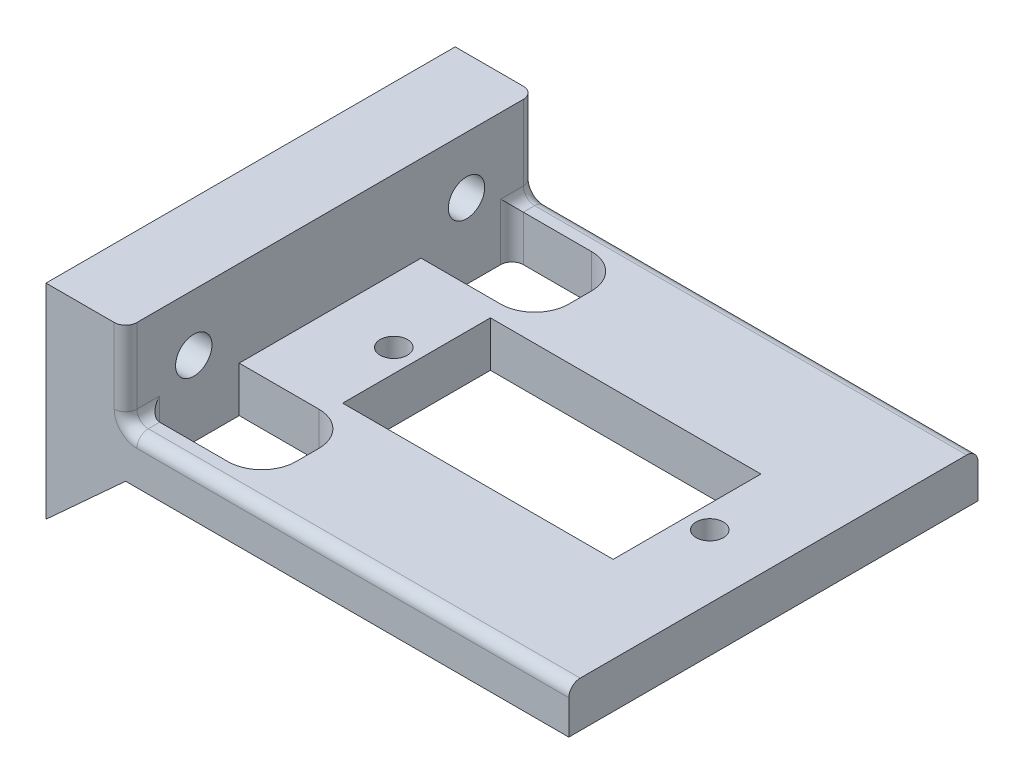
SolidWorks part; units mm, degrees
ref_plane "Front Plane" through (0, 0, 0) normal (0, 0, 1) x (1, 0, 0)
ref_plane "Top Plane" through (0, 0, 0) normal (0, 1, 0) x (1, 0, 0)
ref_plane "Right Plane" through (0, 0, 0) normal (1, 0, 0) x (0, 0, -1)
sketch "Servo_shelf_profile" plane through (0, 0, 0) normal (0, 1, 0) x (1, 0, 0)
  line L1 (-21, -18) -> (25, -18)
  line L2 (-21, -18) -> (-21, 18)
  line L3 (-21, 18) -> (25, 18)
  line L4 (25, -18) -> (25, 18)
  dimension "D1" = 46
  dimension "D2" = 36
  dimension "D3" = 25
  dimension "D4" = 18
extrude "Servo_shelf" add sketch "Servo_shelf_profile" along normal blind 4 from offset 21.4
sketch "Rear_clamping_block_profile" plane through (0, 0, 0) normal (0, 0, 1) x (1, 0, 0)
  line L1 (-21, 23) -> (-14, 23)
  line L2 (-21, 23) -> (-21, 33)
  line L3 (-21, 33) -> (-14, 33)
  line L4 (-14, 23) -> (-14, 33)
  dimension "D1" = 7
  dimension "D2" = 10
  dimension "D3" = 14
  dimension "D4" = 23
extrude "Rear_clamping_block" add sketch "Rear_clamping_block_profile" along normal blind 36 from offset 18 offset against normal yes
sketch "Servo_body_window_profile" plane through (0, 0, 0) normal (0, 1, 0) x (1, 0, 0)
  line L1 (-6.4, -6.5) -> (17.4, -6.5)
  line L2 (-6.4, -6.5) -> (-6.4, 6.5)
  line L3 (-6.4, 6.5) -> (17.4, 6.5)
  line L4 (17.4, -6.5) -> (17.4, 6.5)
  dimension "D1" = 23.8
  dimension "D2" = 13
  dimension "D3" = 17.4
  dimension "D4" = 6.5
extrude "Servo_body_window" cut sketch "Servo_body_window_profile" along normal through all from offset 20.4
sketch "Yaw_servo_M2_fasteners_profile" plane through (0, 0, 0) normal (0, 1, 0) x (1, 0, 0)
  circle A0 centre (-9, 0) radius 1.3
  circle A1 centre (20, 0) radius 1.3
  dimension "D1" = 2.6
  dimension "D2" = 2.6
  dimension "D3" = 20
  dimension "D4" = 9
extrude "Yaw_servo_M2_fasteners_SUPERSEDED_owned_servo" [suppressed] cut sketch "Yaw_servo_M2_fasteners_profile" along normal through all from offset 20.4
sketch "Left_nut_access_profile" plane through (0, 0, 0) normal (0, 1, 0) x (1, 0, 0)
  line L1 (-14, 8) -> (-4, 8)
  line L2 (-14, 8) -> (-14, 16)
  line L3 (-14, 16) -> (-4, 16)
  line L4 (-4, 8) -> (-4, 16)
  dimension "D1" = 10
  dimension "D2" = 8
  dimension "D3" = 4
  dimension "D4" = 8
extrude "Left_nut_access" cut sketch "Left_nut_access_profile" along normal through all from offset 20
sketch "Right_nut_access_profile" plane through (0, 0, 0) normal (0, 1, 0) x (1, 0, 0)
  line L1 (-14, -16) -> (-4, -16)
  line L2 (-14, -16) -> (-14, -8)
  line L3 (-14, -8) -> (-4, -8)
  line L4 (-4, -16) -> (-4, -8)
  dimension "D1" = 10
  dimension "D2" = 8
  dimension "D3" = 4
  dimension "D4" = 8
extrude "Right_nut_access" cut sketch "Right_nut_access_profile" along normal through all from offset 20
sketch "Rear_clamping_M3_profile" plane through (0, 0, 0) normal (1, 0, 0) x (0, 0, -1)
  circle A0 centre (12, 28) radius 1.6
  circle A1 centre (-12, 28) radius 1.6
  dimension "D1" = 3.2
  dimension "D2" = 3.2
  dimension "D3" = 12
  dimension "D4" = 12
  dimension "D5" = 28
extrude "Rear_clamping_M3_holes" cut sketch "Rear_clamping_M3_profile" along normal blind 11 from offset 25 offset against normal yes
fillet "Fillet1" radius 3 4 edges at (-4, 23.4, 16) (-4, 23.4, 8) (-4, 23.4, -16) (-4, 23.4, -8)
fillet "Fillet2" radius 1 8 edges at (-14, 25.4, -17) (-14, 25.4, 17) (-14, 23.4, 16) (-14, 23.4, -16) (-14, 29.2, 18) (5.5, 25.4, 18) (-14, 29.2, -18) (5.5, 25.4, -18)
sketch "Sketch1" plane through (0, 0, -18) normal (0, 0, -1) x (-1, 0, 0)
  line L0 (14, 21.4) -> (21, 15)
  line L1 (21, 15) -> (21, 21.4)
  line L2 (21, 21.4) -> (14, 21.4)
extrude "Boss-Extrude1" add sketch "Sketch1" against normal up to surface (36 mm away) contours L0 L1 L2 up to face at (-5.0592, 26.2265, 18)
sketch "Owned_SG90_M2_ear_holes_profile" plane through (0, 0, 0) normal (0, 1, 0) x (1, 0, 0)
  circle A0 centre (-8.4, 0) radius 1.2
  circle A1 centre (19.4, 0) radius 1.2
  dimension "D1" = 2.4
  dimension "D2" = 2.4
extrude "Owned_SG90_M2_ear_holes" cut sketch "Owned_SG90_M2_ear_holes_profile" along normal through all from offset 20.4
